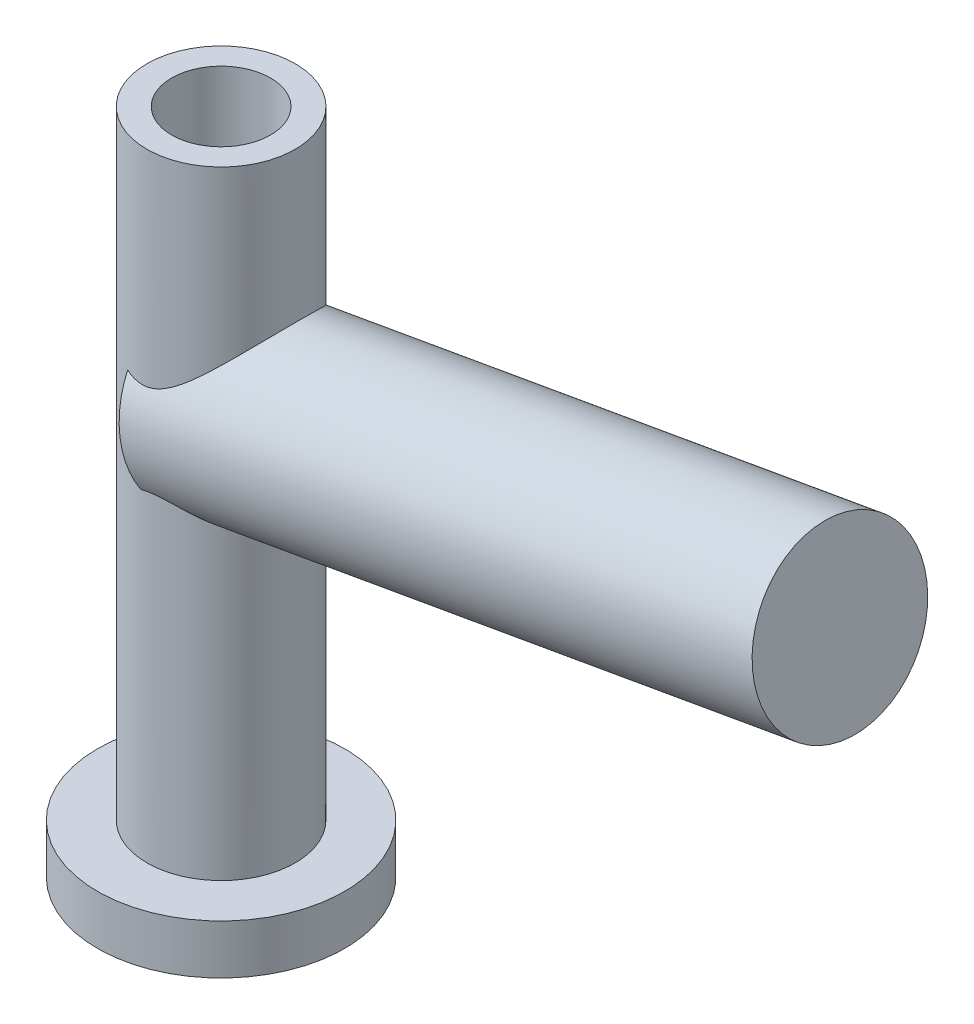
SolidWorks part; units mm, degrees
ref_plane "Front Plane" through (0, 0, 0) normal (0, 0, 1) x (1, 0, 0)
ref_plane "Top Plane" through (0, 0, 0) normal (0, 1, 0) x (1, 0, 0)
ref_plane "Right Plane" through (0, 0, 0) normal (1, 0, 0) x (0, 0, -1)
sketch "Sketch1" plane through (0, 0, 0) normal (0, 0, 1) x (1, 0, 0)
  line L0 (0, 202.5) -> (0, -202.5)
  line L1 (0, -202.5) -> (75, -202.5)
  line L2 (75, -202.5) -> (75, -172.5)
  line L3 (75, -172.5) -> (45, -172.5)
  line L4 (45, -172.5) -> (45, 202.5)
  line L5 (45, 202.5) -> (0, 202.5)
  point P4 (0, 0)
  dimension "D1" = 75
  dimension "D2" = 30
  dimension "D3" = 405
  dimension "D4" = 45
revolve "Revolve1" add sketch "Sketch1" angle 360 about L0
ref_axis "Axis1" through (0, 0, -82.5) along (0, 0, 1)
ref_plane "Plane1" through (0, 0, 0) normal (0.9848, 0.1736, 0) x (0, 0, 1)
sketch "Sketch2" plane through (0, 0, 0) normal (0.9848, 0.1736, 0) x (0, 0, 1)
  circle A0 centre (0, -49.4236) radius 52.5
  ellipse E0 centre (0, -199.4236) end of major axis (-45, -199.4236) minor radius 7.8142 construction
  dimension "D1" = 105
  dimension "D2" = 150
extrude "Boss-Extrude1" add sketch "Sketch2" along normal blind 390
sketch "Sketch3" plane through (0, 202.5, 0) normal (0, 1, 0) x (1, 0, 0)
  circle A0 centre (0, 0) radius 30
  dimension "D1" = 60
extrude "Cut-Extrude1" cut sketch "Sketch3" against normal through all
